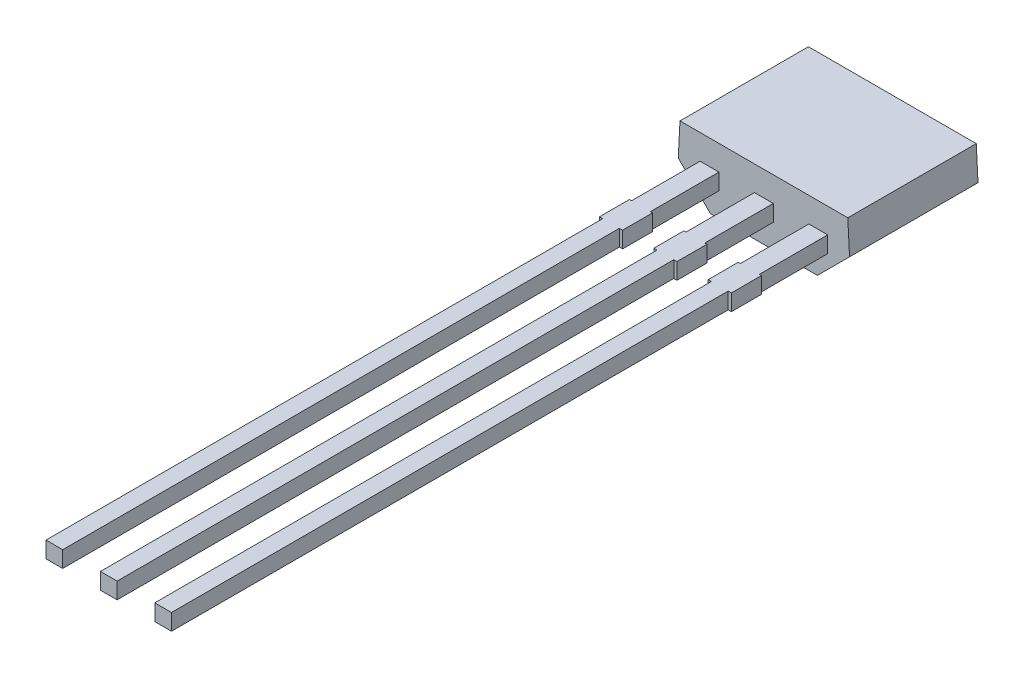
SolidWorks part; units mm, degrees
ref_plane "Front Plane" through (0, 0, 0) normal (0, 0, 1) x (1, 0, 0)
ref_plane "Top Plane" through (0, 0, 0) normal (0, 1, 0) x (1, 0, 0)
ref_plane "Right Plane" through (0, 0, 0) normal (1, 0, 0) x (0, 0, -1)
sketch "Sketch1" plane through (0, 0, 0) normal (0, 1, 0) x (1, 0, 0)
  line L1 (-2, 0) -> (2, 0)
  line L2 (-2, 0) -> (-2, 3)
  line L3 (-2, 3) -> (2, 3)
  line L4 (2, 0) -> (2, 3)
  point P4 (0, 0)
  dimension "D1" = 4
  dimension "D2" = 3
extrude "Boss-Extrude1" add sketch "Sketch1" along normal blind 0.77 contours L1 L4 L3 L2
sketch "Sketch3" plane through (0, 0, 0) normal (0, -1, 0) x (1, 0, 0)
  line L1 (-2, -3) -> (2, -3)
  line L2 (-2, -3) -> (-2, 0)
  line L3 (-2, 0) -> (2, 0)
  line L4 (2, -3) -> (2, 0)
extrude "Boss-Extrude2" add sketch "Sketch3" along normal blind 0.75
chamfer "Chamfer1" distance 0.75 angle 45 2 edges at (2, -0.75, -1.5) (-2, -0.75, -1.5)
chamfer "Chamfer2" distance 0.77 angle 3 2 edges at (-2, 0.77, -1.5) (2, 0.77, -1.5) first distance on face at (-2, 0.385, -1.5) first distance on face at (2, 0.385, -1.5)
sketch "Sketch4" plane through (0, 0, 0) normal (0, 0, 1) x (1, 0, 0)
  line L22 (-1.49, -0.19) -> (-1.05, -0.19)
  line L23 (-1.49, -0.19) -> (-1.49, 0.19)
  line L24 (-1.49, 0.19) -> (-1.05, 0.19)
  line L25 (-1.05, -0.19) -> (-1.05, 0.19)
  line L26 (-1.49, -0.19) -> (-1.05, 0.19) construction
  line L27 (-1.49, 0.19) -> (-1.05, -0.19) construction
  point P0 (0, 0)
  point P14 (-1.27, 0)
  dimension "D1" = 1.27
  dimension "D2" = 0.44
  dimension "D3" = 0.38
extrude "Boss-Extrude3" add sketch "Sketch4" along normal blind 1.6
sketch "Sketch5" plane through (0, 0, 1.6) normal (0, 0, 1) x (1, 0, 0)
  line L0 (-1.05, 0.19) -> (-1.49, 0.19) construction
  line L1 (-1.54, -0.19) -> (-1, -0.19)
  line L2 (-1.54, -0.19) -> (-1.54, 0.19)
  line L3 (-1.54, 0.19) -> (-1, 0.19)
  line L4 (-1, -0.19) -> (-1, 0.19)
  line L5 (-1.54, -0.19) -> (-1, 0.19) construction
  line L6 (-1.54, 0.19) -> (-1, -0.19) construction
  line L7 (-1.49, -0.19) -> (-1.05, -0.19) construction
  point P0 (-1.27, 0)
  point P7 (-1.27, 0.19)
  point P8 (-1.27, 0.19)
  dimension "D1" = 0.54
extrude "Boss-Extrude4" add sketch "Sketch5" along normal blind 0.7
sketch "Sketch6" plane through (0, 0, 2.3) normal (0, 0, 1) x (1, 0, 0)
  line L0 (-1, 0.19) -> (-1.54, 0.19) construction
  line L1 (-1.465, -0.19) -> (-1.075, -0.19)
  line L2 (-1.465, -0.19) -> (-1.465, 0.19)
  line L3 (-1.465, 0.19) -> (-1.075, 0.19)
  line L4 (-1.075, -0.19) -> (-1.075, 0.19)
  line L5 (-1.465, -0.19) -> (-1.075, 0.19) construction
  line L6 (-1.465, 0.19) -> (-1.075, -0.19) construction
  line L7 (-1.54, -0.19) -> (-1, -0.19) construction
  point P0 (-1.27, 0)
  point P9 (0, 0)
  point P10 (-1.27, 0.19)
  dimension "D1" = 0.39
extrude "Boss-Extrude5" add sketch "Sketch6" along normal blind 13
pattern_linear "LPattern1" count 3 spacing 1.27 along (1, 0, 0) of "Boss-Extrude3", "Boss-Extrude5", "Boss-Extrude4"
